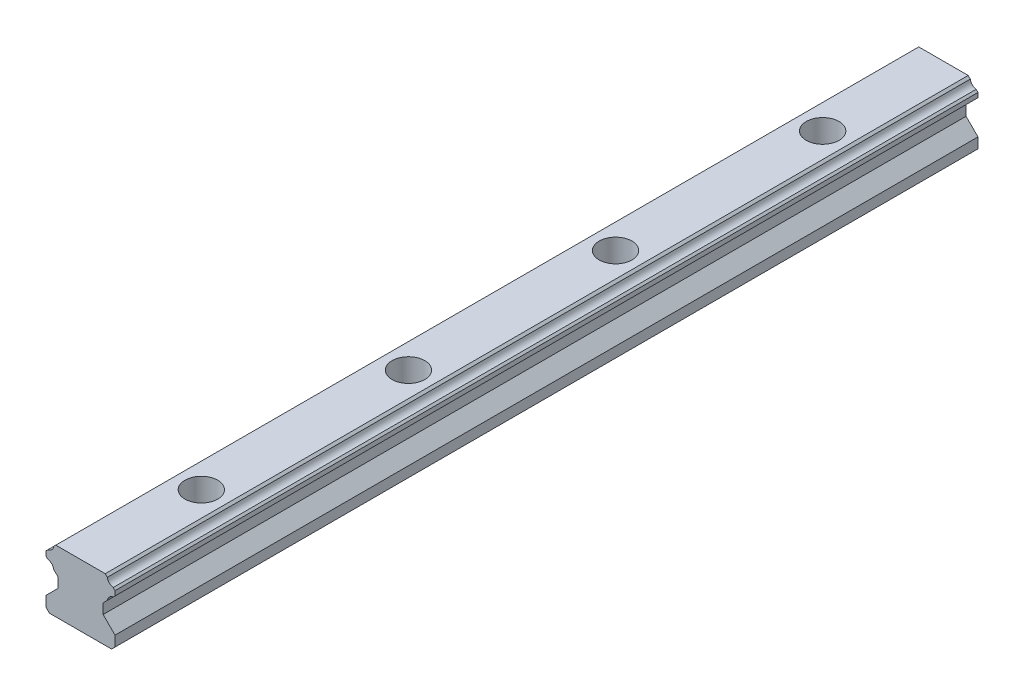
SolidWorks part; units mm, degrees
material "Plain Carbon Steel"
ref_plane "Front Plane" through (0, 0, 0) normal (0, 0, 1) x (1, 0, 0)
ref_plane "Top Plane" through (0, 0, 0) normal (0, 1, 0) x (1, 0, 0)
ref_plane "Right Plane" through (0, 0, 0) normal (1, 0, 0) x (0, 0, -1)
sketch "Sketch1" plane through (0, 0, 0) normal (0, 0, 1) x (1, 0, 0)
  line L0 (0, 13.3681) -> (0, -3.2505) construction
  line L1 (-6.55, -4.115) -> (-6.55, -7.045)
  line L2 (-6.55, -5.58) -> (0, -5.58) construction
  line L3 (-6.55, -7.045) -> (-10, -10.495)
  line L4 (-10, -10.495) -> (-10, -13.495)
  line L5 (-10, -13.495) -> (-9, -14.495)
  line L6 (-9, -14.495) -> (0, -14.495)
  line L7 (-6.55, -4.115) -> (-7.7681, -2.8969)
  line L8 (-10, -0.665) -> (-10, 0.665)
  line L9 (-10, 0.665) -> (-9.4697, 1.1953)
  line L10 (-7.16, 3.505) -> (0, 3.505)
  line L11 (-10, -0.665) -> (-10, -10.495) construction
  line L12 (-10, 0) -> (0, 0) construction
  line L13 (-7.7681, 2.8969) -> (-7.16, 3.505)
  line L14 (-9.4697, -1.1953) -> (-10, -0.665)
  line L15 (0, 3.505) -> (0, -14.495)
  arc A0 (-9.4697, 1.1953) -> (-7.7681, 2.8969) centre (-9.7486, 3.1758) ccw
  arc A1 (-9.4697, -1.1953) -> (-7.7681, -2.8969) centre (-9.7486, -3.1758) cw
  dimension "D10" = 4
  dimension "D1" = 2.93
  dimension "D2" = 6.55
  dimension "D3" = 9
  dimension "D4" = 7.16
  dimension "D5" = 3
  dimension "D6" = 1.33
  dimension "D7" = 18
  dimension "D8" = 45
  dimension "D9" = 45
  dimension "D11" = 0.75
  dimension "D12" = 0.86
extrude "Boss-Extrude1" add sketch "Sketch1" along normal blind 125
mirror "Mirror1" about plane through (0, 3.505, 125) normal (-1, 0, 0) of "Boss-Extrude1"
sketch "Sketch2" plane through (0, 3.505, 0) normal (0, 1, 0) x (1, 0, 0)
  line L0 (0, 130.187) -> (0, 31.9327) construction
  line L1 (7.16, 0) -> (-7.16, 0) construction
  circle A0 centre (0, -30) radius 3
  dimension "D1" = 6
  dimension "D2" = 30
extrude "Cut-Extrude1" cut sketch "Sketch2" against normal through all
sketch "Sketch3" plane through (0, 3.505, 0) normal (0, 1, 0) x (1, 0, 0)
  circle A0 centre (0, -30) radius 4.75
  dimension "D1" = 9.5
extrude "Cut-Extrude2" cut sketch "Sketch3" against normal blind 8.5
pattern_linear "LPattern1" count 100 spacing 60 along (0, 0, 1) of "Cut-Extrude1", "Cut-Extrude2"
mirror "Mirror2" about plane through (-9.7486, -3.1758, 0) normal (0, 0, -1) of bodies 106
equation "\"length\"= 250mm"
equation "\"D1@Boss-Extrude1\"  = \"length\" /2"
equation "\"M5_tap\"=4.2mm\t\t\t\t\t\t\t' Below you can do mesurements as follows: cm, mm, ft, in, m, "
equation "\"M5_clearence\"=5.5mm"
equation "\"M6_tap\"=5mm"
equation "\"M6_clearence\"=6.6mm"
equation "\"work_area_width\"=1100mm"
equation "\"work_area_depth\"=900mm"
